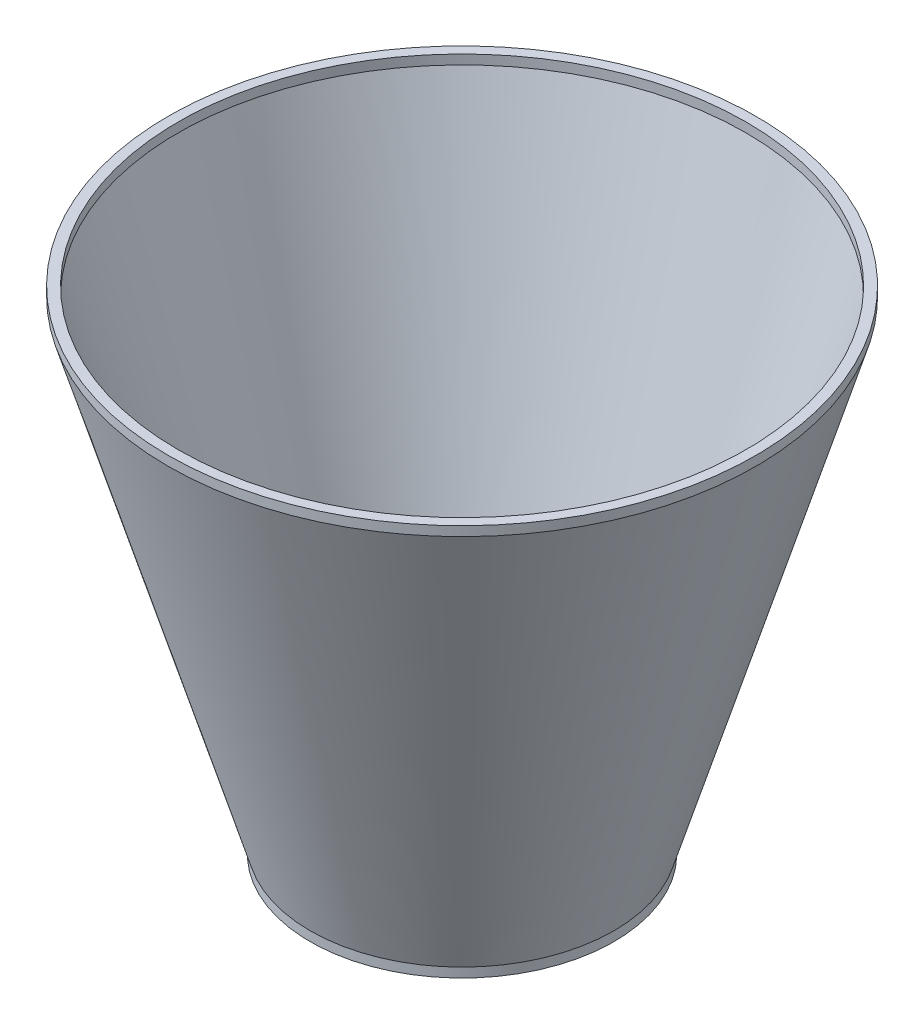
SolidWorks part; units mm, degrees
ref_plane "Front Plane" through (0, 0, 0) normal (0, 0, 1) x (1, 0, 0)
ref_plane "Top Plane" through (0, 0, 0) normal (0, 1, 0) x (1, 0, 0)
ref_plane "Right Plane" through (0, 0, 0) normal (1, 0, 0) x (0, 0, -1)
sketch "Sketch1" plane through (0, 0, 0) normal (0, 0, 1) x (1, 0, 0)
  line L0 (-30, 0) -> (-60, 100)
  line L1 (0, 0) -> (0, 68.8325) construction
  line L2 (-32.0881, 0) -> (-62.0881, 100)
  line L3 (-60, 100) -> (-62.0881, 100)
  line L4 (-30, 0) -> (-32.0881, 0)
  line L5 (-31.9157, -0.5747) -> (-61.9157, 99.4253) construction
  dimension "D1" = 30
  dimension "D2" = 60
  dimension "D3" = 100
  dimension "D4" = 0
  dimension "D5" = 2
revolve "Revolve1" add sketch "Sketch1" angle 360 about L1
sketch "Sketch2" plane through (0, 0, 0) normal (0, -1, 0) x (1, 0, 0)
  circle A0 centre (0, 0) radius 32.0881
  circle A1 centre (0, 0) radius 30
extrude "Boss-Extrude1" add sketch "Sketch2" along normal blind 2
sketch "Sketch3" plane through (0, 100, 0) normal (0, 1, 0) x (1, 0, 0)
  circle A0 centre (0, 0) radius 60
  circle A1 centre (0, 0) radius 62.0881
extrude "Boss-Extrude2" add sketch "Sketch3" along normal blind 2
